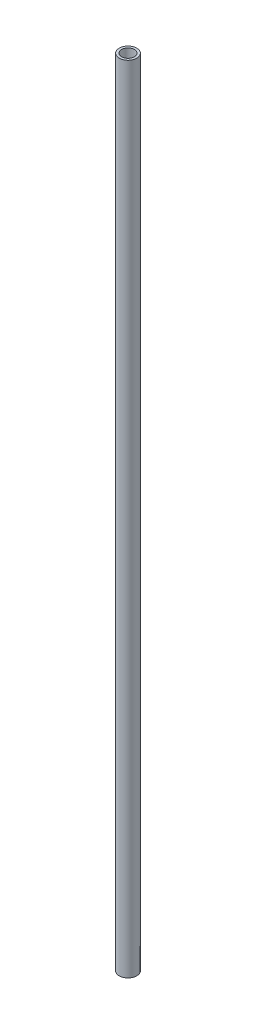
SolidWorks part; units mm, degrees
ref_plane "Front Plane" through (0, 0, 0) normal (0, 0, 1) x (1, 0, 0)
ref_plane "Top Plane" through (0, 0, 0) normal (0, 1, 0) x (1, 0, 0)
ref_plane "Right Plane" through (0, 0, 0) normal (1, 0, 0) x (0, 0, -1)
sketch "Sketch1" plane through (0, 0, 0) normal (0, 1, 0) x (1, 0, 0)
  circle A0 centre (0, 0) radius 3.625
  circle A1 centre (0, 0) radius 4.975
  dimension "D1" = 9.95
  dimension "D2" = 7.25
extrude "Boss-Extrude1" add sketch "Sketch1" along normal blind 452
ref_axis "Axis1" through (0, 452, 0) along (0, -1, 0)
